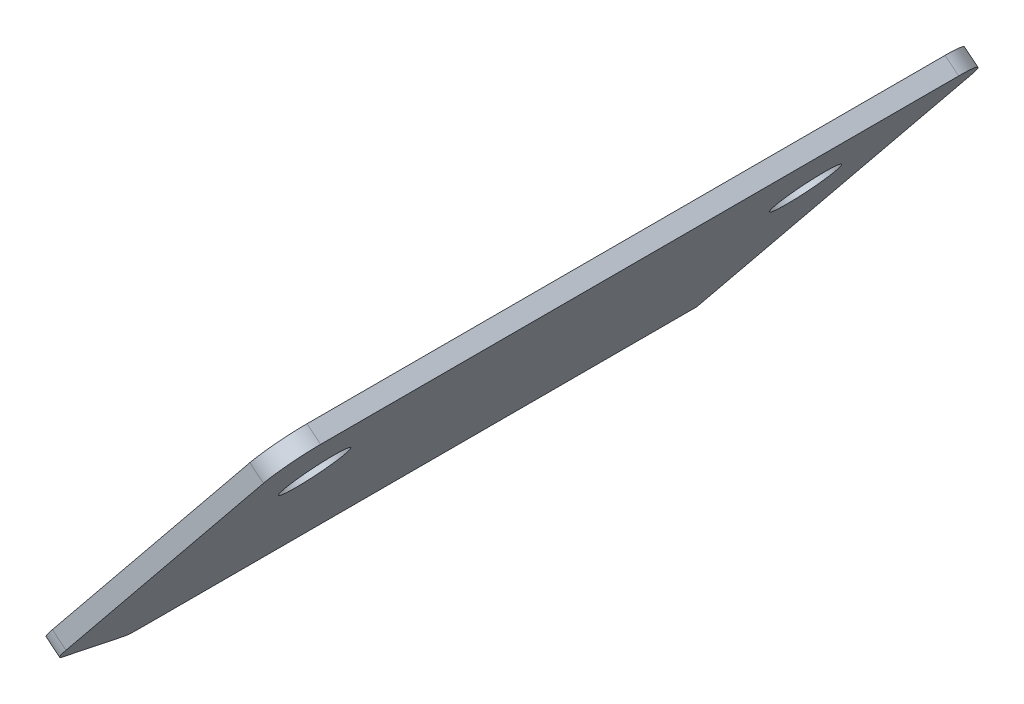
SolidWorks part; units mm, degrees
ref_plane "Front Plane" through (0, 0, 0) normal (0, 0, 1) x (1, 0, 0)
ref_plane "Top Plane" through (0, 0, 0) normal (0, 1, 0) x (1, 0, 0)
ref_plane "Right Plane" through (0, 0, 0) normal (1, 0, 0) x (0, 0, -1)
sketch "Sketch1" plane through (0, 0, 0) normal (0, 0, 1) x (1, 0, 0)
  line L0 (-449.0277, -411.7335) -> (-556.5822, -544.2683)
  line L1 (-117.475, -3.175) -> (-513.0493, -490.6246) construction
  line L2 (-556.5822, -544.2683) -> (-561.5128, -540.267)
  line L3 (-561.5128, -540.267) -> (-453.9584, -407.7322)
  line L4 (-453.9584, -407.7322) -> (-449.0277, -411.7335)
  circle A1 centre (-609.6, -609.6) radius 84.1375 construction
  point P8 (-513.0493, -490.6246)
  dimension "D1" = 6.35
  dimension "D2" = 101.6
extrude "Boss-Extrude1" add sketch "Sketch1" along normal up to surface (256.54 mm away)
sketch "Sketch2" plane through (-74.2066, 60.22, 0) normal (-0.7765, 0.6301, 0) x (0, 0, 1)
  line L0 (128.27, -602.653) -> (121.92, -704.253) construction
  line L1 (256.54, -602.653) -> (0, -602.653) construction
  line L2 (243.84, -704.253) -> (0, -704.253) construction
  line L3 (213.995, -653.453) -> (36.195, -653.453) construction
  circle A0 centre (213.995, -653.453) radius 11.1125
  circle A1 centre (36.195, -653.453) radius 11.1125
  point P8 (125.095, -653.453)
  dimension "D2" = 22.225
  dimension "D1" = 177.8
extrude "Cut-Extrude1" cut sketch "Sketch2" against normal up to next
sketch "Sketch3" plane through (-69.2759, 56.2187, 0) normal (0.7765, -0.6301, 0) x (0, 0, -1)
  line L0 (-205.74, -773.3382) -> (-256.54, -735.2382)
  line L1 (-256.54, -773.3382) -> (0, -773.3382) construction
  line L2 (-256.54, -773.3382) -> (-256.54, -602.653) construction
  dimension "D1" = 50.8
  dimension "D2" = 38.1
extrude "Cut-Extrude2" cut sketch "Sketch3" against normal through all and the other way through all
fillet "Fillet1" radius 12.7 4 edges at (-535.0394, -512.6835, 256.54) (-559.0475, -542.2677, 205.74) (-451.4931, -409.7328, 0) (-451.4931, -409.7328, 256.54)
